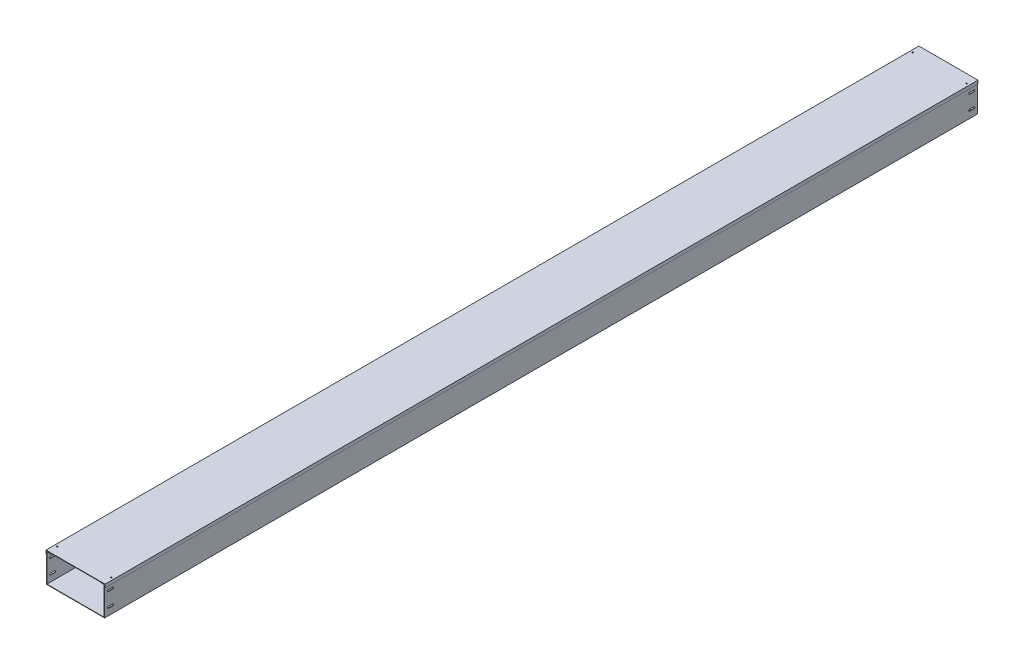
SolidWorks part; units mm, degrees
material "Plain Carbon Steel"
ref_plane "Front Plane" through (0, 0, 0) normal (0, 0, 1) x (1, 0, 0)
ref_plane "Top Plane" through (0, 0, 0) normal (0, 1, 0) x (1, 0, 0)
ref_plane "Right Plane" through (0, 0, 0) normal (1, 0, 0) x (0, 0, -1)
sketch "DuctSketch" plane through (0, 0, 0) normal (0, 0, 1) x (1, 0, 0)
  line L0 (-100, -50) -> (100, -50)
  line L1 (100, -50) -> (100, 50)
  line L2 (-100, -50) -> (-100, 50)
  line L3 (-100, 50) -> (-85, 50)
  line L4 (100, 50) -> (85, 50)
  line L5 (-100, 50) -> (100, -50) construction
  point P3 (0, 0)
  dimension "Height" = 100
  dimension "Width" = 200
  dimension "D1" = 15
extrude "Extrusion" add sketch "DuctSketch" along normal blind 3000 thin thin type one direction reverse wall 1.5
sketch "FilterSketch" plane through (0, 0, 0) normal (0, 0, 1) x (1, 0, 0)
  line L1 (100, 100) -> (-100, 100)
  line L2 (100, 100) -> (100, 0)
  line L3 (100, 0) -> (-100, 0)
  line L4 (-100, 100) -> (-100, 0)
  dimension "NominalHeight" = 100
  dimension "NominalWidth" = 200
sketch "Sketch1" plane through (0, 0, 0) normal (1, 0, 0) x (0, 0, -1)
  line L0 (0, 0) -> (-40, 0) construction
  line L2 (-20, 0) -> (-20, -50) construction
  line L4 (-20, 0) -> (-20, 50) construction
  line L6 (-27.5, 25) -> (-12.5, 25) construction
  line L7 (-27.5, 28) -> (-12.5, 28)
  line L8 (-27.5, 22) -> (-12.5, 22)
  line L9 (-27.5, -25) -> (-12.5, -25) construction
  line L10 (-27.5, -22) -> (-12.5, -22)
  line L11 (-27.5, -28) -> (-12.5, -28)
  line L14 (0, -50) -> (0, 50) construction
  line L18 (-3000, -50) -> (0, -50) construction
  line L19 (-3000, 50) -> (0, 50) construction
  arc A0 (-27.5, 28) -> (-27.5, 22) centre (-27.5, 25) ccw
  arc A1 (-12.5, 22) -> (-12.5, 28) centre (-12.5, 25) ccw
  arc A2 (-27.5, -22) -> (-27.5, -28) centre (-27.5, -25) ccw
  arc A3 (-12.5, -28) -> (-12.5, -22) centre (-12.5, -25) ccw
  point P13 (-20, 25)
  point P19 (-20, -25)
  dimension "D1" = 3
  dimension "D2" = 15
  dimension "D5" = 40
extrude "Cut-Extrude1" cut sketch "Sketch1" against normal through all and the other way through all
sketch "Sketch2" plane through (0, 0, 0) normal (1, 0, 0) x (0, 0, -1)
  line L0 (-3000, 0) -> (-2960, 0) construction
  line L1 (-2980, 0) -> (-2980, 50) construction
  line L2 (-2980, 0) -> (-2980, -50) construction
  line L3 (-3000, -50) -> (-3000, 50) construction
  line L4 (-2987.5, 25) -> (-2972.5, 25) construction
  line L5 (-2987.5, 28) -> (-2972.5, 28)
  line L6 (-2987.5, 22) -> (-2972.5, 22)
  line L7 (-2987.5, -25) -> (-2972.5, -25) construction
  line L8 (-2987.5, -22) -> (-2972.5, -22)
  line L9 (-2987.5, -28) -> (-2972.5, -28)
  line L10 (-3000, 50) -> (0, 50) construction
  line L11 (-3000, -50) -> (0, -50) construction
  arc A0 (-2987.5, 28) -> (-2987.5, 22) centre (-2987.5, 25) ccw
  arc A1 (-2972.5, 22) -> (-2972.5, 28) centre (-2972.5, 25) ccw
  arc A2 (-2987.5, -22) -> (-2987.5, -28) centre (-2987.5, -25) ccw
  arc A3 (-2972.5, -28) -> (-2972.5, -22) centre (-2972.5, -25) ccw
  point P10 (-2980, 25)
  point P16 (-2980, -25)
  dimension "D5" = 3
  dimension "D1" = 40
  dimension "D4" = 15
extrude "Cut-Extrude2" cut sketch "Sketch2" against normal through all and the other way through all
sketch "Sketch3" plane through (0, 50, 0) normal (0, 1, 0) x (1, 0, 0)
  line L12 (-85, 0) -> (-100, 0) construction
  line L14 (92.5, 0) -> (92.5, -60) construction
  line L17 (-92.5, 0) -> (-92.5, -60) construction
  line L18 (100, 0) -> (85, 0) construction
  circle A0 centre (-92.5, -30) radius 2
  circle A1 centre (92.5, -30) radius 2
  dimension "D2" = 30
  dimension "D1" = 4
extrude "Cut-Extrude3" cut sketch "Sketch3" against normal up to next
sketch "Sketch4" plane through (0, 50, 0) normal (0, 1, 0) x (1, 0, 0)
  line L0 (-92.5, -3000) -> (-92.5, -2940) construction
  line L1 (-85, -3000) -> (-100, -3000) construction
  line L2 (92.5, -3000) -> (92.5, -2940) construction
  line L3 (100, -3000) -> (85, -3000) construction
  circle A0 centre (-92.5, -2970) radius 2
  circle A1 centre (92.5, -2970) radius 2
  dimension "D1" = 4
  dimension "D2" = 30
extrude "Cut-Extrude4" cut sketch "Sketch4" against normal up to next
sketch "Sketch5" plane through (0, 0, 0) normal (0, 0, 1) x (1, 0, 0)
  line L0 (-100, 40) -> (-100, 50)
  line L1 (-100, 50) -> (-100, -50) construction
  line L2 (-100, 50) -> (100, 50)
  line L3 (100, 50) -> (100, 40)
  line L4 (100, -50) -> (100, 50) construction
  dimension "D1" = 10
extrude "Extrude-Thin1" add sketch "Sketch5" along normal blind 3000 separate body thin thin type one direction reverse wall 1.5
sketch "Sketch6" plane through (0, 51.5, 0) normal (0, -1, 0) x (1, 0, 0)
  circle A2 centre (92.5, 30) radius 2 construction
  circle A3 centre (92.5, 30) radius 2
  circle A6 centre (-92.5, 30) radius 2 construction
  circle A7 centre (-92.5, 30) radius 2
extrude "Cut-Extrude5" cut sketch "Sketch6" along normal up to next (1.5 mm away)
sketch "Sketch7" plane through (0, 51.5, 0) normal (0, 1, 0) x (1, 0, 0)
  circle A0 centre (-92.5, -2970) radius 2 construction
  circle A1 centre (92.5, -2970) radius 2 construction
  circle A2 centre (-92.5, -2970) radius 2
  circle A3 centre (92.5, -2970) radius 2
extrude "Cut-Extrude6" cut sketch "Sketch7" against normal up to next (1.5 mm away)
equation "\"Cut-Extrude1\"= IIF ( \"Length@Extrusion\" < = 50mm , \"suppressed\" , \"unsuppressed\" )"
equation "\"Cut-Extrude2\"= if ( \"Length@Extrusion\" < = 100mm , \"suppressed\" , \"unsuppressed\" )"
equation "\"Thickness@Extrude-Thin1\"=\"Thickness@Extrusion\""
equation "\"Length@Extrude-Thin1\"=\"Length@Extrusion\""
equation "\"Cut-Extrude3\"= IIF ( \"Length@Extrusion\" < = 50mm , \"suppressed\" , \"unsuppressed\" )"
equation "\"Cut-Extrude4\" = IIF ( \"Length@Extrusion\" < = 100mm , \"suppressed\" , \"unsuppressed\" )"
equation "\"Cut-Extrude5\"= IIF ( \"Length@Extrusion\" < = 50mm , \"suppressed\" , \"unsuppressed\" )"
equation "\"Cut-Extrude6\"= IIF ( \"Length@Extrusion\" < = 100mm , \"suppressed\" , \"unsuppressed\" )"
